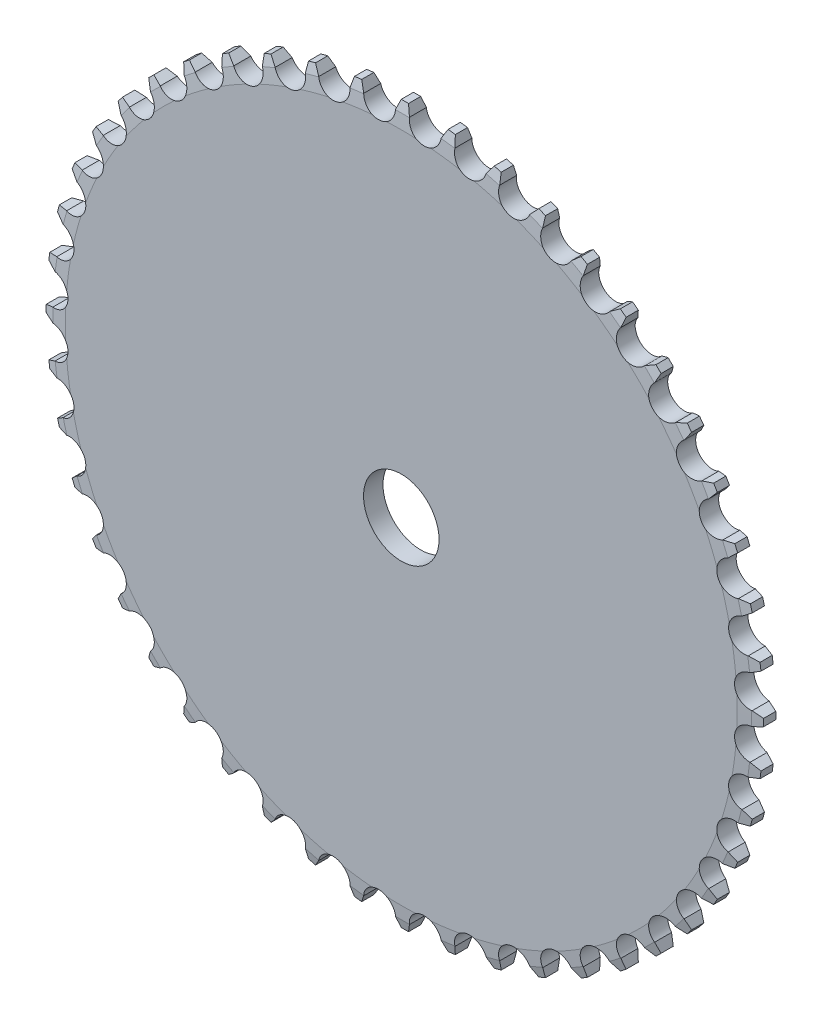
SolidWorks part; units mm, degrees
material "AISI 1045 Steel, cold drawn"
ref_plane "Front Plane" through (0, 0, 0) normal (0, 0, 1) x (1, 0, 0)
ref_plane "Top Plane" through (0, 0, 0) normal (0, 1, 0) x (1, 0, 0)
ref_plane "Right Plane" through (0, 0, 0) normal (1, 0, 0) x (0, 0, -1)
sketch "Sketch1" plane through (0, 0, 0) normal (0, 0, 1) x (1, 0, 0)
  line L0 (0, 0) -> (-4.5942, 70.0933) construction
  line L1 (0, 0) -> (4.5942, 70.0933) construction
  line L2 (0, 0) -> (0, 75.4253) construction
  line L3 (-0.762, 75.4215) -> (0.762, 75.4215)
  line L4 (0.762, 75.4215) -> (1.457, 73.512)
  line L5 (9.089, 74.8757) -> (8.1507, 73.0733)
  line L6 (18.7845, 73.0487) -> (17.619, 71.3842)
  line L7 (10.6, 74.6767) -> (11.0398, 72.6929)
  line L8 (9.089, 74.8757) -> (10.6, 74.6767)
  line L9 (28.1585, 69.9719) -> (26.7857, 68.4738)
  line L10 (20.2565, 72.6543) -> (20.4336, 70.63)
  line L11 (18.7845, 73.0487) -> (20.2565, 72.6543)
  line L12 (37.0508, 65.6979) -> (35.4942, 64.3917)
  line L13 (29.5665, 69.3887) -> (29.4779, 67.3587)
  line L14 (28.1585, 69.9719) -> (29.5665, 69.3887)
  line L15 (45.3091, 60.2997) -> (43.5954, 59.2079)
  line L16 (38.3706, 64.9359) -> (38.0178, 62.9348)
  line L17 (37.0508, 65.6979) -> (38.3706, 64.9359)
  line L18 (52.7922, 53.8698) -> (50.9506, 53.0111)
  line L19 (46.5182, 59.372) -> (45.9072, 57.434)
  line L20 (45.3091, 60.2997) -> (46.5182, 59.372)
  line L21 (59.372, 46.5182) -> (57.434, 45.9072)
  line L22 (53.8698, 52.7922) -> (53.0111, 50.9506)
  line L23 (52.7922, 53.8698) -> (53.8698, 52.7922)
  line L24 (64.9359, 38.3706) -> (62.9348, 38.0178)
  line L25 (60.2997, 45.3091) -> (59.2079, 43.5954)
  line L26 (59.372, 46.5182) -> (60.2997, 45.3091)
  line L27 (69.3887, 29.5665) -> (67.3587, 29.4779)
  line L28 (65.6979, 37.0508) -> (64.3917, 35.4942)
  line L29 (64.9359, 38.3706) -> (65.6979, 37.0508)
  line L30 (72.6543, 20.2565) -> (70.63, 20.4336)
  line L31 (69.9719, 28.1585) -> (68.4738, 26.7857)
  line L32 (69.3887, 29.5665) -> (69.9719, 28.1585)
  line L33 (74.6767, 10.6) -> (72.6929, 11.0398)
  line L34 (73.0487, 18.7845) -> (71.3842, 17.619)
  line L35 (72.6543, 20.2565) -> (73.0487, 18.7845)
  line L36 (75.4215, 0.762) -> (73.512, 1.457)
  line L37 (74.8757, 9.089) -> (73.0733, 8.1507)
  line L38 (74.6767, 10.6) -> (74.8757, 9.089)
  line L39 (74.8757, -9.089) -> (73.0733, -8.1507)
  line L40 (75.4215, -0.762) -> (73.512, -1.457)
  line L41 (75.4215, 0.762) -> (75.4215, -0.762)
  line L42 (73.0487, -18.7845) -> (71.3842, -17.619)
  line L43 (74.6767, -10.6) -> (72.6929, -11.0398)
  line L44 (74.8757, -9.089) -> (74.6767, -10.6)
  line L45 (69.9719, -28.1585) -> (68.4738, -26.7857)
  line L46 (72.6543, -20.2565) -> (70.63, -20.4336)
  line L47 (73.0487, -18.7845) -> (72.6543, -20.2565)
  line L48 (65.6979, -37.0508) -> (64.3917, -35.4942)
  line L49 (69.3887, -29.5665) -> (67.3587, -29.4779)
  line L50 (69.9719, -28.1585) -> (69.3887, -29.5665)
  line L51 (60.2997, -45.3091) -> (59.2079, -43.5954)
  line L52 (64.9359, -38.3706) -> (62.9348, -38.0178)
  line L53 (65.6979, -37.0508) -> (64.9359, -38.3706)
  line L54 (53.8698, -52.7922) -> (53.0111, -50.9506)
  line L55 (59.372, -46.5182) -> (57.434, -45.9072)
  line L56 (60.2997, -45.3091) -> (59.372, -46.5182)
  line L57 (46.5182, -59.372) -> (45.9072, -57.434)
  line L58 (52.7922, -53.8698) -> (50.9506, -53.0111)
  line L59 (53.8698, -52.7922) -> (52.7922, -53.8698)
  line L60 (38.3706, -64.9359) -> (38.0178, -62.9348)
  line L61 (45.3091, -60.2997) -> (43.5954, -59.2079)
  line L62 (46.5182, -59.372) -> (45.3091, -60.2997)
  line L63 (29.5665, -69.3887) -> (29.4779, -67.3587)
  line L64 (37.0508, -65.6979) -> (35.4942, -64.3917)
  line L65 (38.3706, -64.9359) -> (37.0508, -65.6979)
  line L66 (20.2565, -72.6543) -> (20.4336, -70.63)
  line L67 (28.1585, -69.9719) -> (26.7857, -68.4738)
  line L68 (29.5665, -69.3887) -> (28.1585, -69.9719)
  line L69 (10.6, -74.6767) -> (11.0398, -72.6929)
  line L70 (18.7845, -73.0487) -> (17.619, -71.3842)
  line L71 (20.2565, -72.6543) -> (18.7845, -73.0487)
  line L72 (0.762, -75.4215) -> (1.457, -73.512)
  line L73 (9.089, -74.8757) -> (8.1507, -73.0733)
  line L74 (10.6, -74.6767) -> (9.089, -74.8757)
  line L75 (-9.089, -74.8757) -> (-8.1507, -73.0733)
  line L76 (-0.762, -75.4215) -> (-1.457, -73.512)
  line L77 (0.762, -75.4215) -> (-0.762, -75.4215)
  line L78 (-18.7845, -73.0487) -> (-17.619, -71.3842)
  line L79 (-10.6, -74.6767) -> (-11.0398, -72.6929)
  line L80 (-9.089, -74.8757) -> (-10.6, -74.6767)
  line L81 (-28.1585, -69.9719) -> (-26.7857, -68.4738)
  line L82 (-20.2565, -72.6543) -> (-20.4336, -70.63)
  line L83 (-18.7845, -73.0487) -> (-20.2565, -72.6543)
  line L84 (-37.0508, -65.6979) -> (-35.4942, -64.3917)
  line L85 (-29.5665, -69.3887) -> (-29.4779, -67.3587)
  line L86 (-28.1585, -69.9719) -> (-29.5665, -69.3887)
  line L87 (-45.3091, -60.2997) -> (-43.5954, -59.2079)
  line L88 (-38.3706, -64.9359) -> (-38.0178, -62.9348)
  line L89 (-37.0508, -65.6979) -> (-38.3706, -64.9359)
  line L90 (-52.7922, -53.8698) -> (-50.9506, -53.0111)
  line L91 (-46.5182, -59.372) -> (-45.9072, -57.434)
  line L92 (-45.3091, -60.2997) -> (-46.5182, -59.372)
  line L93 (-59.372, -46.5182) -> (-57.434, -45.9072)
  line L94 (-53.8698, -52.7922) -> (-53.0111, -50.9506)
  line L95 (-52.7922, -53.8698) -> (-53.8698, -52.7922)
  line L96 (-64.9359, -38.3706) -> (-62.9348, -38.0178)
  line L97 (-60.2997, -45.3091) -> (-59.2079, -43.5954)
  line L98 (-59.372, -46.5182) -> (-60.2997, -45.3091)
  line L99 (-69.3887, -29.5665) -> (-67.3587, -29.4779)
  line L100 (-65.6979, -37.0508) -> (-64.3917, -35.4942)
  line L101 (-64.9359, -38.3706) -> (-65.6979, -37.0508)
  line L102 (-72.6543, -20.2565) -> (-70.63, -20.4336)
  line L103 (-69.9719, -28.1585) -> (-68.4738, -26.7857)
  line L104 (-69.3887, -29.5665) -> (-69.9719, -28.1585)
  line L105 (-74.6767, -10.6) -> (-72.6929, -11.0398)
  line L106 (-73.0487, -18.7845) -> (-71.3842, -17.619)
  line L107 (-72.6543, -20.2565) -> (-73.0487, -18.7845)
  line L108 (-75.4215, -0.762) -> (-73.512, -1.457)
  line L109 (-74.8757, -9.089) -> (-73.0733, -8.1507)
  line L110 (-74.6767, -10.6) -> (-74.8757, -9.089)
  line L111 (-74.8757, 9.089) -> (-73.0733, 8.1507)
  line L112 (-75.4215, 0.762) -> (-73.512, 1.457)
  line L113 (-75.4215, -0.762) -> (-75.4215, 0.762)
  line L114 (-73.0487, 18.7845) -> (-71.3842, 17.619)
  line L115 (-74.6767, 10.6) -> (-72.6929, 11.0398)
  line L116 (-74.8757, 9.089) -> (-74.6767, 10.6)
  line L117 (-69.9719, 28.1585) -> (-68.4738, 26.7857)
  line L118 (-72.6543, 20.2565) -> (-70.63, 20.4336)
  line L119 (-73.0487, 18.7845) -> (-72.6543, 20.2565)
  line L120 (-65.6979, 37.0508) -> (-64.3917, 35.4942)
  line L121 (-69.3887, 29.5665) -> (-67.3587, 29.4779)
  line L122 (-69.9719, 28.1585) -> (-69.3887, 29.5665)
  line L123 (-60.2997, 45.3091) -> (-59.2079, 43.5954)
  line L124 (-64.9359, 38.3706) -> (-62.9348, 38.0178)
  line L125 (-65.6979, 37.0508) -> (-64.9359, 38.3706)
  line L126 (-53.8698, 52.7922) -> (-53.0111, 50.9506)
  line L127 (-59.372, 46.5182) -> (-57.434, 45.9072)
  line L128 (-60.2997, 45.3091) -> (-59.372, 46.5182)
  line L129 (-46.5182, 59.372) -> (-45.9072, 57.434)
  line L130 (-52.7922, 53.8698) -> (-50.9506, 53.0111)
  line L131 (-53.8698, 52.7922) -> (-52.7922, 53.8698)
  line L132 (-38.3706, 64.9359) -> (-38.0178, 62.9348)
  line L133 (-45.3091, 60.2997) -> (-43.5954, 59.2079)
  line L134 (-46.5182, 59.372) -> (-45.3091, 60.2997)
  line L135 (-29.5665, 69.3887) -> (-29.4779, 67.3587)
  line L136 (-37.0508, 65.6979) -> (-35.4942, 64.3917)
  line L137 (-38.3706, 64.9359) -> (-37.0508, 65.6979)
  line L138 (-20.2565, 72.6543) -> (-20.4336, 70.63)
  line L139 (-28.1585, 69.9719) -> (-26.7857, 68.4738)
  line L140 (-29.5665, 69.3887) -> (-28.1585, 69.9719)
  line L141 (-10.6, 74.6767) -> (-11.0398, 72.6929)
  line L142 (-18.7845, 73.0487) -> (-17.619, 71.3842)
  line L143 (-20.2565, 72.6543) -> (-18.7845, 73.0487)
  line L144 (-0.762, 75.4215) -> (-1.457, 73.512)
  line L145 (-9.089, 74.8757) -> (-8.1507, 73.0733)
  line L146 (-10.6, 74.6767) -> (-9.089, 74.8757)
  circle A0 centre (0, 0) radius 75.4253 construction
  circle A1 centre (0, 0) radius 70.2437 construction
  circle A2 centre (0, 0) radius 7.9375
  circle A3 centre (0, 0) radius 73.5264 construction
  arc A4 (1.457, 73.512) -> (4.5942, 70.0933) centre (4.8137, 73.4436) ccw
  arc A5 (4.5942, 70.0933) -> (8.1507, 73.0733) centre (4.8137, 73.4436) ccw
  arc A6 (13.7039, 68.894) -> (17.619, 71.3842) centre (14.3589, 72.1869) ccw
  arc A7 (11.0398, 72.6929) -> (13.7039, 68.894) centre (14.3589, 72.1869) ccw
  arc A8 (22.5791, 66.5159) -> (26.7857, 68.4738) centre (23.6583, 69.6952) ccw
  arc A9 (20.4336, 70.63) -> (22.5791, 66.5159) centre (23.6583, 69.6952) ccw
  arc A10 (31.068, 62.9997) -> (35.4942, 64.3917) centre (32.553, 66.0109) ccw
  arc A11 (29.4779, 67.3587) -> (31.068, 62.9997) centre (32.553, 66.0109) ccw
  arc A12 (39.0253, 58.4055) -> (43.5954, 59.2079) centre (40.8906, 61.1971) ccw
  arc A13 (38.0178, 62.9348) -> (39.0253, 58.4055) centre (40.8906, 61.1971) ccw
  arc A14 (46.3149, 52.812) -> (50.9506, 53.0111) centre (48.5286, 55.3363) ccw
  arc A15 (45.9072, 57.434) -> (46.3149, 52.812) centre (48.5286, 55.3363) ccw
  arc A16 (52.812, 46.3149) -> (57.434, 45.9072) centre (55.3363, 48.5286) ccw
  arc A17 (53.0111, 50.9506) -> (52.812, 46.3149) centre (55.3363, 48.5286) ccw
  arc A18 (58.4055, 39.0253) -> (62.9348, 38.0178) centre (61.1971, 40.8906) ccw
  arc A19 (59.2079, 43.5954) -> (58.4055, 39.0253) centre (61.1971, 40.8906) ccw
  arc A20 (62.9997, 31.068) -> (67.3587, 29.4779) centre (66.0109, 32.553) ccw
  arc A21 (64.3917, 35.4942) -> (62.9997, 31.068) centre (66.0109, 32.553) ccw
  arc A22 (66.5159, 22.5791) -> (70.63, 20.4336) centre (69.6952, 23.6583) ccw
  arc A23 (68.4738, 26.7857) -> (66.5159, 22.5791) centre (69.6952, 23.6583) ccw
  arc A24 (68.894, 13.7039) -> (72.6929, 11.0398) centre (72.1869, 14.3589) ccw
  arc A25 (71.3842, 17.619) -> (68.894, 13.7039) centre (72.1869, 14.3589) ccw
  arc A26 (70.0933, 4.5942) -> (73.512, 1.457) centre (73.4436, 4.8137) ccw
  arc A27 (73.0733, 8.1507) -> (70.0933, 4.5942) centre (73.4436, 4.8137) ccw
  arc A28 (70.0933, -4.5942) -> (73.0733, -8.1507) centre (73.4436, -4.8137) ccw
  arc A29 (73.512, -1.457) -> (70.0933, -4.5942) centre (73.4436, -4.8137) ccw
  arc A30 (68.894, -13.7039) -> (71.3842, -17.619) centre (72.1869, -14.3589) ccw
  arc A31 (72.6929, -11.0398) -> (68.894, -13.7039) centre (72.1869, -14.3589) ccw
  arc A32 (66.5159, -22.5791) -> (68.4738, -26.7857) centre (69.6952, -23.6583) ccw
  arc A33 (70.63, -20.4336) -> (66.5159, -22.5791) centre (69.6952, -23.6583) ccw
  arc A34 (62.9997, -31.068) -> (64.3917, -35.4942) centre (66.0109, -32.553) ccw
  arc A35 (67.3587, -29.4779) -> (62.9997, -31.068) centre (66.0109, -32.553) ccw
  arc A36 (58.4055, -39.0253) -> (59.2079, -43.5954) centre (61.1971, -40.8906) ccw
  arc A37 (62.9348, -38.0178) -> (58.4055, -39.0253) centre (61.1971, -40.8906) ccw
  arc A38 (52.812, -46.3149) -> (53.0111, -50.9506) centre (55.3363, -48.5286) ccw
  arc A39 (57.434, -45.9072) -> (52.812, -46.3149) centre (55.3363, -48.5286) ccw
  arc A40 (46.3149, -52.812) -> (45.9072, -57.434) centre (48.5286, -55.3363) ccw
  arc A41 (50.9506, -53.0111) -> (46.3149, -52.812) centre (48.5286, -55.3363) ccw
  arc A42 (39.0253, -58.4055) -> (38.0178, -62.9348) centre (40.8906, -61.1971) ccw
  arc A43 (43.5954, -59.2079) -> (39.0253, -58.4055) centre (40.8906, -61.1971) ccw
  arc A44 (31.068, -62.9997) -> (29.4779, -67.3587) centre (32.553, -66.0109) ccw
  arc A45 (35.4942, -64.3917) -> (31.068, -62.9997) centre (32.553, -66.0109) ccw
  arc A46 (22.5791, -66.5159) -> (20.4336, -70.63) centre (23.6583, -69.6952) ccw
  arc A47 (26.7857, -68.4738) -> (22.5791, -66.5159) centre (23.6583, -69.6952) ccw
  arc A48 (13.7039, -68.894) -> (11.0398, -72.6929) centre (14.3589, -72.1869) ccw
  arc A49 (17.619, -71.3842) -> (13.7039, -68.894) centre (14.3589, -72.1869) ccw
  arc A50 (4.5942, -70.0933) -> (1.457, -73.512) centre (4.8137, -73.4436) ccw
  arc A51 (8.1507, -73.0733) -> (4.5942, -70.0933) centre (4.8137, -73.4436) ccw
  arc A52 (-4.5942, -70.0933) -> (-8.1507, -73.0733) centre (-4.8137, -73.4436) ccw
  arc A53 (-1.457, -73.512) -> (-4.5942, -70.0933) centre (-4.8137, -73.4436) ccw
  arc A54 (-13.7039, -68.894) -> (-17.619, -71.3842) centre (-14.3589, -72.1869) ccw
  arc A55 (-11.0398, -72.6929) -> (-13.7039, -68.894) centre (-14.3589, -72.1869) ccw
  arc A56 (-22.5791, -66.5159) -> (-26.7857, -68.4738) centre (-23.6583, -69.6952) ccw
  arc A57 (-20.4336, -70.63) -> (-22.5791, -66.5159) centre (-23.6583, -69.6952) ccw
  arc A58 (-31.068, -62.9997) -> (-35.4942, -64.3917) centre (-32.553, -66.0109) ccw
  arc A59 (-29.4779, -67.3587) -> (-31.068, -62.9997) centre (-32.553, -66.0109) ccw
  arc A60 (-39.0253, -58.4055) -> (-43.5954, -59.2079) centre (-40.8906, -61.1971) ccw
  arc A61 (-38.0178, -62.9348) -> (-39.0253, -58.4055) centre (-40.8906, -61.1971) ccw
  arc A62 (-46.3149, -52.812) -> (-50.9506, -53.0111) centre (-48.5286, -55.3363) ccw
  arc A63 (-45.9072, -57.434) -> (-46.3149, -52.812) centre (-48.5286, -55.3363) ccw
  arc A64 (-52.812, -46.3149) -> (-57.434, -45.9072) centre (-55.3363, -48.5286) ccw
  arc A65 (-53.0111, -50.9506) -> (-52.812, -46.3149) centre (-55.3363, -48.5286) ccw
  arc A66 (-58.4055, -39.0253) -> (-62.9348, -38.0178) centre (-61.1971, -40.8906) ccw
  arc A67 (-59.2079, -43.5954) -> (-58.4055, -39.0253) centre (-61.1971, -40.8906) ccw
  arc A68 (-62.9997, -31.068) -> (-67.3587, -29.4779) centre (-66.0109, -32.553) ccw
  arc A69 (-64.3917, -35.4942) -> (-62.9997, -31.068) centre (-66.0109, -32.553) ccw
  arc A70 (-66.5159, -22.5791) -> (-70.63, -20.4336) centre (-69.6952, -23.6583) ccw
  arc A71 (-68.4738, -26.7857) -> (-66.5159, -22.5791) centre (-69.6952, -23.6583) ccw
  arc A72 (-68.894, -13.7039) -> (-72.6929, -11.0398) centre (-72.1869, -14.3589) ccw
  arc A73 (-71.3842, -17.619) -> (-68.894, -13.7039) centre (-72.1869, -14.3589) ccw
  arc A74 (-70.0933, -4.5942) -> (-73.512, -1.457) centre (-73.4436, -4.8137) ccw
  arc A75 (-73.0733, -8.1507) -> (-70.0933, -4.5942) centre (-73.4436, -4.8137) ccw
  arc A76 (-70.0933, 4.5942) -> (-73.0733, 8.1507) centre (-73.4436, 4.8137) ccw
  arc A77 (-73.512, 1.457) -> (-70.0933, 4.5942) centre (-73.4436, 4.8137) ccw
  arc A78 (-68.894, 13.7039) -> (-71.3842, 17.619) centre (-72.1869, 14.3589) ccw
  arc A79 (-72.6929, 11.0398) -> (-68.894, 13.7039) centre (-72.1869, 14.3589) ccw
  arc A80 (-66.5159, 22.5791) -> (-68.4738, 26.7857) centre (-69.6952, 23.6583) ccw
  arc A81 (-70.63, 20.4336) -> (-66.5159, 22.5791) centre (-69.6952, 23.6583) ccw
  arc A82 (-62.9997, 31.068) -> (-64.3917, 35.4942) centre (-66.0109, 32.553) ccw
  arc A83 (-67.3587, 29.4779) -> (-62.9997, 31.068) centre (-66.0109, 32.553) ccw
  arc A84 (-58.4055, 39.0253) -> (-59.2079, 43.5954) centre (-61.1971, 40.8906) ccw
  arc A85 (-62.9348, 38.0178) -> (-58.4055, 39.0253) centre (-61.1971, 40.8906) ccw
  arc A86 (-52.812, 46.3149) -> (-53.0111, 50.9506) centre (-55.3363, 48.5286) ccw
  arc A87 (-57.434, 45.9072) -> (-52.812, 46.3149) centre (-55.3363, 48.5286) ccw
  arc A88 (-46.3149, 52.812) -> (-45.9072, 57.434) centre (-48.5286, 55.3363) ccw
  arc A89 (-50.9506, 53.0111) -> (-46.3149, 52.812) centre (-48.5286, 55.3363) ccw
  arc A90 (-39.0253, 58.4055) -> (-38.0178, 62.9348) centre (-40.8906, 61.1971) ccw
  arc A91 (-43.5954, 59.2079) -> (-39.0253, 58.4055) centre (-40.8906, 61.1971) ccw
  arc A92 (-31.068, 62.9997) -> (-29.4779, 67.3587) centre (-32.553, 66.0109) ccw
  arc A93 (-35.4942, 64.3917) -> (-31.068, 62.9997) centre (-32.553, 66.0109) ccw
  arc A94 (-22.5791, 66.5159) -> (-20.4336, 70.63) centre (-23.6583, 69.6952) ccw
  arc A95 (-26.7857, 68.4738) -> (-22.5791, 66.5159) centre (-23.6583, 69.6952) ccw
  arc A96 (-13.7039, 68.894) -> (-11.0398, 72.6929) centre (-14.3589, 72.1869) ccw
  arc A97 (-17.619, 71.3842) -> (-13.7039, 68.894) centre (-14.3589, 72.1869) ccw
  arc A98 (-4.5942, 70.0933) -> (-1.457, 73.512) centre (-4.8137, 73.4436) ccw
  arc A99 (-8.1507, 73.0733) -> (-4.5942, 70.0933) centre (-4.8137, 73.4436) ccw
  point P11 (0, 75.4215)
  point P14 (0, 73.5264)
  point P15 (0, 0)
  dimension "D1" = 150.8506
  dimension "D2" = 140.4874
  dimension "D3" = 15.875
  dimension "D6" = 1.524
  dimension "D8" = 2.032
  dimension "D7" = 48
  dimension "D4" = 7.5
  dimension "D5" = 3.75
  dimension "D10" = 110
extrude "Boss-Extrude2" add sketch "Sketch1" along normal blind 4.0894 contours A99 L145 L146 L141 A96 A97 L142 L143 L138 A94 A95 L139 L140 L135 A92 A93 L136 L137 L132 A90 A91 L133 L134 L129 A88 A89 L130 L131 L126 A86 A87 L127 L128 L123 A84 A85 L124 L125 L120 A82 A83 L121 L122 L117 A80 A81 L118 L119 L114 A78 A79 region at (0, 73.2882, 0)
sketch "Sketch3" plane through (0, 0, 0) normal (1, 0, 0) x (0, 0, -1)
  line L0 (-3.3274, 75.4215) -> (-3.8487, 73.4575)
  line L1 (-4.0894, 75.4215) -> (0, 75.4215) construction
  line L2 (-3.8487, 73.4575) -> (-4.0894, 70.63)
  line L6 (-2.0447, 75.4215) -> (-2.0447, 71.5759) construction
  line L11 (-3.3274, 75.4215) -> (-3.3274, 76.3648)
  line L12 (-3.3274, 76.3648) -> (-4.7523, 76.3648)
  line L13 (-4.7523, 76.3648) -> (-4.7523, 70.63)
  line L14 (-4.7523, 70.63) -> (-4.0894, 70.63)
  line L15 (0.6629, 70.63) -> (0, 70.63)
  line L16 (0.6629, 76.3648) -> (0.6629, 70.63)
  line L17 (-0.762, 76.3648) -> (0.6629, 76.3648)
  line L18 (-0.762, 75.4215) -> (-0.762, 76.3648)
  line L19 (-0.2407, 73.4575) -> (0, 70.63)
  line L20 (-0.762, 75.4215) -> (-0.2407, 73.4575)
  point P7 (-2.0447, 75.4215)
  dimension "D1" = 2.032
  dimension "D2" = 170
  dimension "D3" = 0.762
ref_axis "Axis1" through (0, 0, 4.0894) along (0, 0, -1)
revolve "Cut-Revolve3" cut sketch "Sketch3" angle 360 about axis through (0, 0, 4.0894) along (0, 0, -1) region at (0, 73.9222, 4.2074) region at (0, 73.9222, -0.118)
